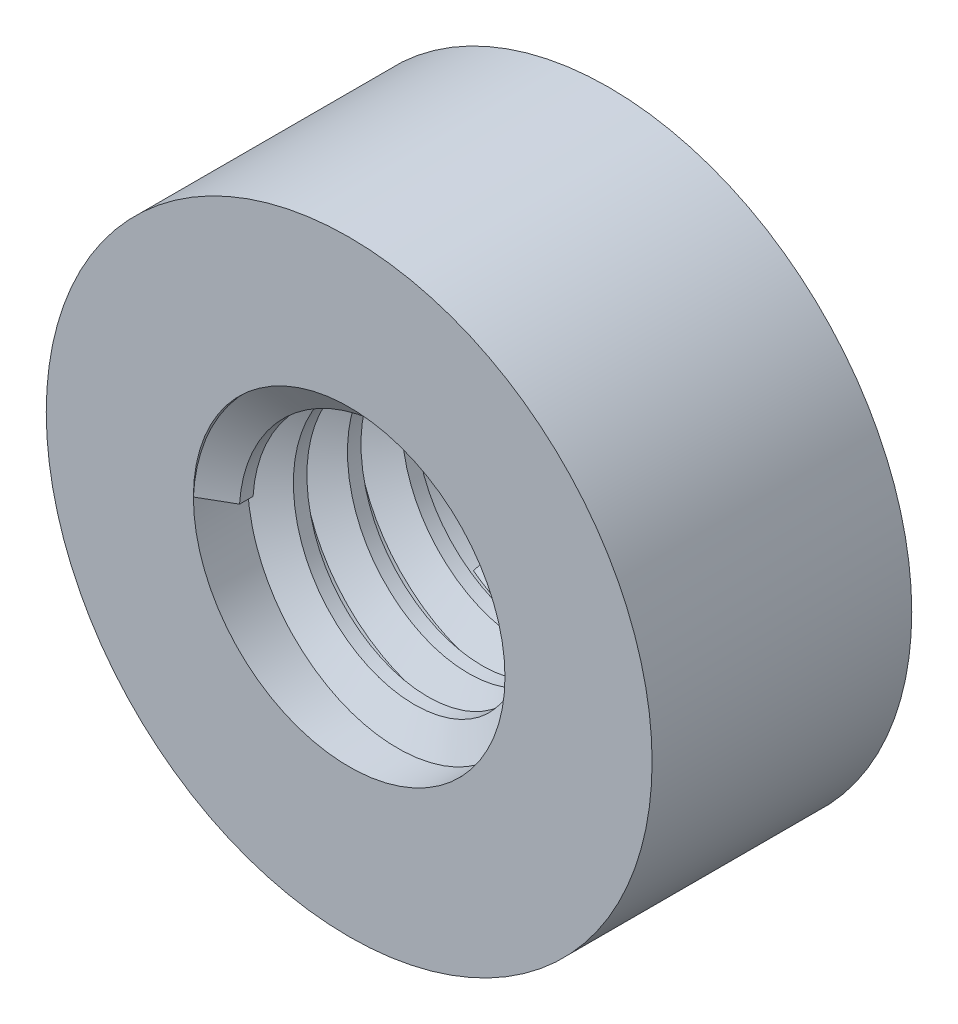
SolidWorks part; units mm, degrees
ref_plane "Front Plane" through (0, 0, 0) normal (0, 0, 1) x (1, 0, 0)
ref_plane "Top Plane" through (0, 0, 0) normal (0, 1, 0) x (1, 0, 0)
ref_plane "Right Plane" through (0, 0, 0) normal (1, 0, 0) x (0, 0, -1)
sketch "Sketch2" plane through (0, 0, 0) normal (0, 0, 1) x (1, 0, 0)
  circle A0 centre (0, 0) radius 2.286
  circle A1 centre (0, 0) radius 4.445
  dimension "D1" = 4.572
  dimension "D2" = 8.89
extrude "Boss-Extrude1" add sketch "Sketch2" along normal blind 3.81
thread "Thread1" pitch 0.7937 method extrude profile "Thread Profile1" start angle 0, offset 0, length 3.048, pitch 0.7937, diameter 4.572
ref_plane "Plane4" through (-2.286, 0, 3.81) normal (0, -1, 0) x (-1, 0, 0)
sketch "Thread Profile1" plane through (-2.286, 0, 3.81) normal (0, -1, 0) x (-1, 0, 0)
  line L0 (0, 0) -> (0, 0.7937) construction
  line L11 (0, 0) -> (0, 0.6945)
  line L12 (0, 0.6945) -> (-0.4296, 0.4465)
  line L13 (-0.4296, 0.4465) -> (-0.4296, 0.248)
  line L15 (-0.4296, 0.248) -> (0, 0)
  line L17 (-0.4296, 0.3473) -> (0, 0.3473) construction
  point P2 (0, 0)
  dimension "Pitch" = 0.7937
  dimension "Profile_Angle" = 60
  dimension "Profile_Land" = 0.1984
  dimension "Profile_Height" = 0.4296
